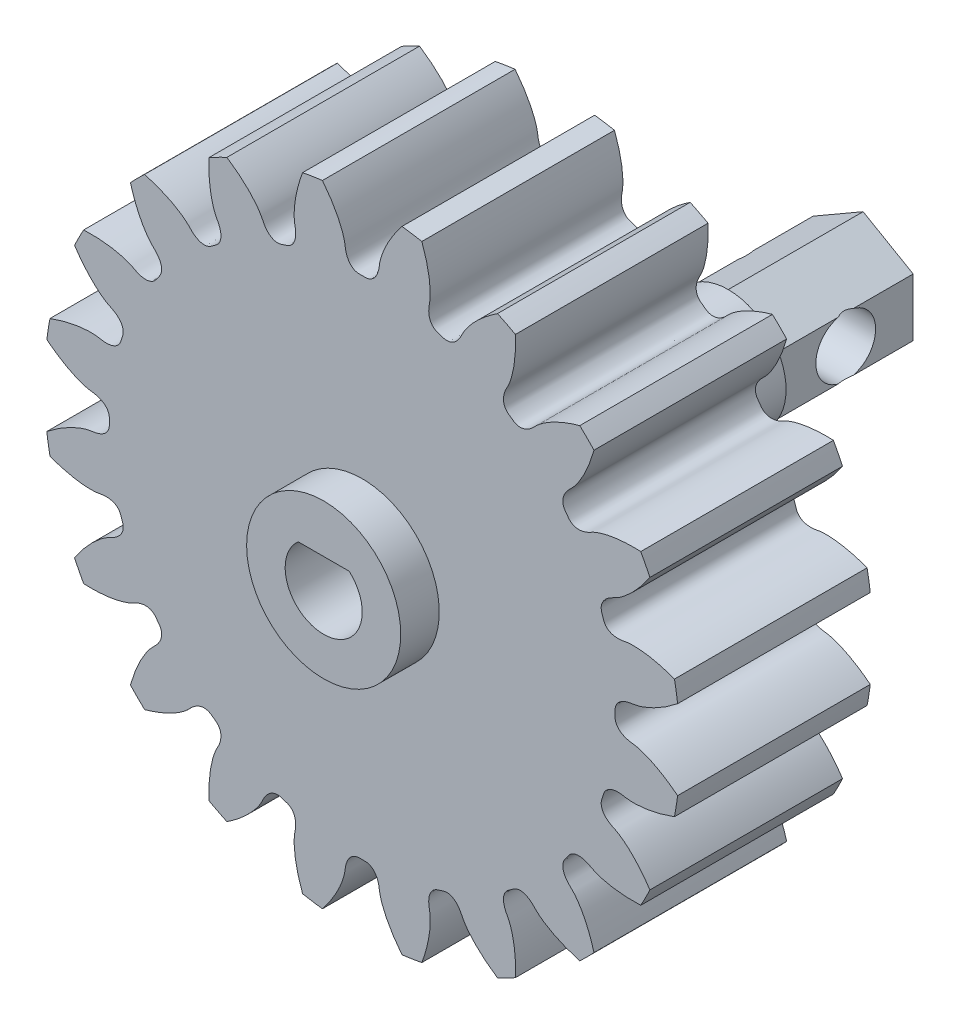
SolidWorks part; units mm, degrees
ref_plane "Front Plane" through (0, 0, 0) normal (0, 0, 1) x (1, 0, 0)
ref_plane "Top Plane" through (0, 0, 0) normal (0, 1, 0) x (1, 0, 0)
ref_plane "Right Plane" through (0, 0, 0) normal (1, 0, 0) x (0, 0, -1)
ref_axis "Axis1" through (0, 0, 55) along (0, 0, -1)
sketch "SketchRevolveSpurAssembly01Pinion" plane through (0, 0, 0) normal (1, 0, 0) x (0, 0, -1)
  line L0 (0, 0) -> (1, 0) construction
  line L1 (-5, 0) -> (-5, 16.5)
  line L2 (-5, 16.5) -> (5, 16.5)
  line L3 (5, 16.5) -> (5, 0)
  line L4 (5, 0) -> (-5, 0)
  dimension "Side1" = 5
  dimension "OutsideRadius" = 16.5
  dimension "Side2" = 5
revolve "SpurAssembly01Pinion" add sketch "SketchRevolveSpurAssembly01Pinion" angle 360 about L0
sketch "SketchToothSpurAssembly01Pinion" plane through (0, 0, 0) normal (0, 0, 1) x (1, 0, 0)
  arc A0 (16.4388, 2.1204) -> (16.4388, -2.1204) centre (0, 0) cw
  spline S0 degree 3 poles (16.4388, -2.1204) (16.3062, -2.0126) (16.1079, -1.8609) (15.8417, -1.6767) (15.6549, -1.5557) (15.4759, -1.4476) (15.3054, -1.3516) (15.1441, -1.2672) (14.9923, -1.1937) (14.8506, -1.1305) (14.7196, -1.0767) (14.5996, -1.0318) (14.491, -0.9949) (14.3942, -0.9653) (14.3096, -0.9423) (14.2375, -0.925) (14.178, -0.9126) (14.0492, -0.8903) (13.9123, -0.8782) (13.7697, -0.8427) (13.6956, -0.8206) (13.6244, -0.795) (13.5557, -0.7654) (13.4893, -0.7311) (13.4248, -0.6913) (13.3623, -0.6446) (13.3021, -0.5892) (13.2452, -0.523) (13.1943, -0.4439) (13.1533, -0.3509) (13.1303, -0.2534) (13.1208, -0.135) (13.1277, 0) (13.1208, 0.135) (13.1303, 0.2534) (13.1533, 0.3509) (13.1943, 0.4439) (13.2452, 0.523) (13.3021, 0.5892) (13.3623, 0.6446) (13.4248, 0.6913) (13.4893, 0.7311) (13.5557, 0.7654) (13.6244, 0.795) (13.6956, 0.8206) (13.7697, 0.8427) (13.9123, 0.8782) (14.0492, 0.8903) (14.178, 0.9126) (14.2375, 0.925) (14.3096, 0.9423) (14.3942, 0.9653) (14.491, 0.9949) (14.5996, 1.0318) (14.7196, 1.0767) (14.8506, 1.1305) (14.9923, 1.1937) (15.1441, 1.2672) (15.3054, 1.3516) (15.4759, 1.4476) (15.6549, 1.5557) (15.8417, 1.6767) (16.1079, 1.8609) (16.3062, 2.0126) (16.4388, 2.1204) knots 0 0 0 0 0.061423 0.08971 0.11638 0.141434 0.164872 0.186693 0.206898 0.225486 0.242459 0.257814 0.271554 0.283677 0.294183 0.303073 0.310347 0.316004 0.350077 0.359568 0.368803 0.377844 0.386769 0.395676 0.404689 0.413963 0.423683 0.434051 0.445256 0.457401 0.47042 0.481067 0.5 0.518933 0.52958 0.542599 0.554744 0.565949 0.576317 0.586037 0.595311 0.604324 0.613231 0.622156 0.631197 0.640432 0.649923 0.683996 0.689653 0.696927 0.705817 0.716323 0.728446 0.742186 0.757541 0.774514 0.793102 0.813307 0.835128 0.858566 0.88362 0.91029 0.938577 1 1 1 1
extrude "ToothExtrudeCutSpurAssembly01Pinion" cut sketch "SketchToothSpurAssembly01Pinion" against normal blind 5 and the other way blind 5
pattern_circular "PatternSpurAssembly01Pinion" count 20 every 18 about axis through (0, 0, 55) along (0, 0, -1) of "ToothExtrudeCutSpurAssembly01Pinion"
sketch "AuxiliarySketchSpurAssembly01Pinion" plane through (0, 0, 0) normal (0, 0, 1) x (1, 0, 0)
  circle A0 centre (0, 0) radius 15 construction
  circle A1 centre (0, 0) radius 14.0954 construction
  circle A2 centre (0, 0) radius 14.1048 construction
  circle A3 centre (0, 0) radius 16.5 construction
  circle A4 centre (0, 0) radius 13.125 construction
  dimension "PitchDiameter" = 30
  dimension "BaseDiameter" = 28.1908
  dimension "FormDiameter" = 28.2095
  dimension "MajorDiameter" = 33
  dimension "MinorDiameter" = 26.25
sketch "Sketch2" plane through (0, 0, -5) normal (0, 0, -1) x (-1, 0, 0)
  circle A0 centre (0, 0) radius 3
extrude "Boss-Extrude1" add sketch "Sketch2" along normal blind 9
sketch "Sketch3" plane through (0, 0, -14) normal (0, 0, -1) x (-1, 0, 0)
  line L0 (0, 3) -> (-2.5981, 1.5)
  line L1 (-2.5981, 1.5) -> (-2.5981, -1.5)
  line L2 (0, -3) -> (0, 3) construction
  line L3 (-2.5981, -1.5) -> (2.5981, 1.5) construction
  line L4 (2.5981, -1.5) -> (-2.5981, 1.5) construction
  line L5 (-2.5981, -1.5) -> (0, -3)
  line L6 (0, -3) -> (2.5981, -1.5)
  line L7 (2.5981, -1.5) -> (2.5981, 1.5)
  line L8 (2.5981, 1.5) -> (0, 3)
  circle A0 centre (0, 0) radius 3 construction
  point P11 (0, 0)
  point P15 (0, 0)
  point P18 (0, 0)
extrude "Boss-Extrude2" add sketch "Sketch3" along normal blind 7
sketch "Sketch4" plane through (2.5981, 0, 0) normal (1, 0, 0) x (0, 0, -1)
  line L0 (14, 1.5) -> (21, -1.5) construction
  circle A0 centre (17.5, 0) radius 1.55
extrude "Cut-Extrude3" cut sketch "Sketch4" against normal up to surface (5.1962 mm away) up to face at (-2.5981, 0, -17.5)
sketch "Sketch5" plane through (0, 0, 5) normal (0, 0, 1) x (1, 0, 0)
  circle A0 centre (0, 0) radius 4
extrude "Boss-Extrude3" add sketch "Sketch5" along normal blind 2
sketch "Sketch6" plane through (0, 0, 7) normal (0, 0, 1) x (1, 0, 0)
  line L0 (0, 0) -> (0, 1.5) construction
  line L1 (-1.3229, 1.5) -> (1.3229, 1.5)
  circle A0 centre (0, 0) radius 2 construction
  arc A1 (1.3229, 1.5) -> (-1.3229, 1.5) centre (0, 0) cw
  point P7 (0, 1.5)
extrude "Cut-Extrude4" cut sketch "Sketch6" against normal blind 8
